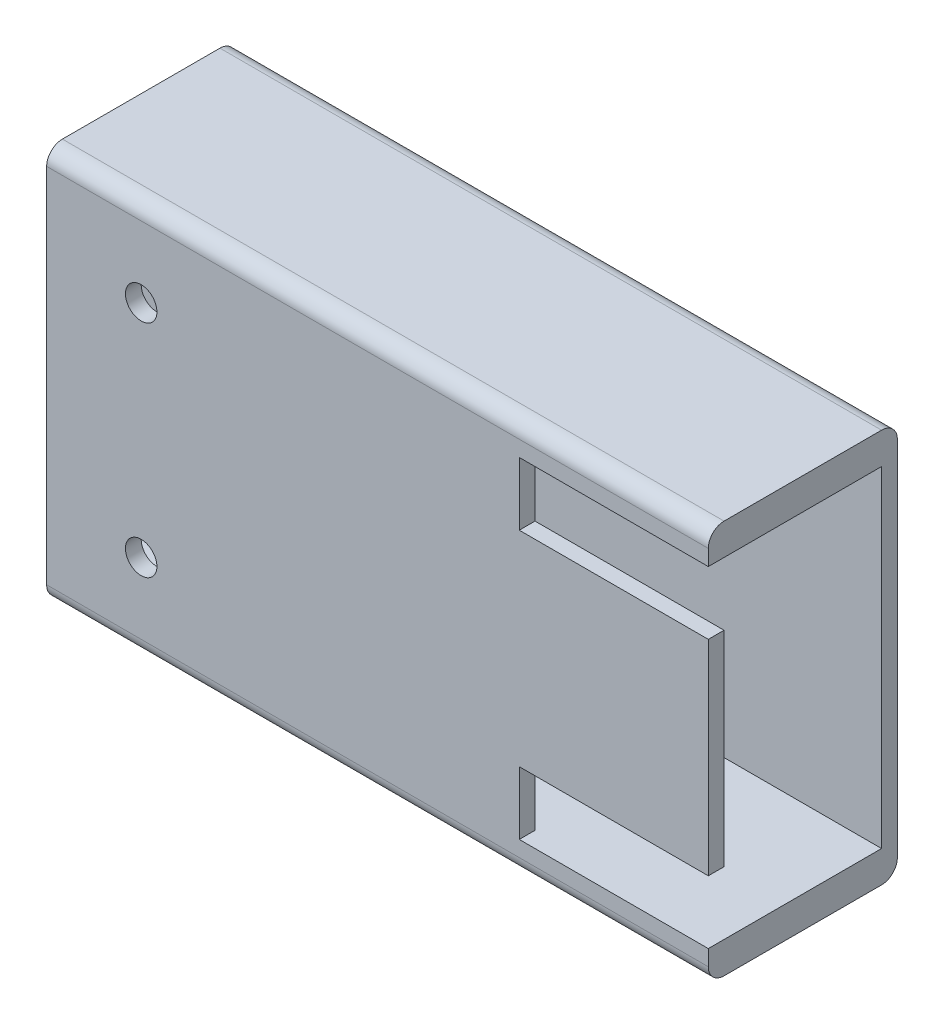
SolidWorks part; units mm, degrees
ref_plane "前视基准面" through (0, 0, 0) normal (0, 0, 1) x (1, 0, 0)
ref_plane "上视基准面" through (0, 0, 0) normal (0, 1, 0) x (1, 0, 0)
ref_plane "右视基准面" through (0, 0, 0) normal (1, 0, 0) x (0, 0, -1)
other "Configuration Table"
sketch "草图1" plane through (0, 0, 0) normal (0, 0, 1) x (1, 0, 0)
  line L0 (21, 12.5) -> (21, -12.5)
  line L1 (-19, 10.5) -> (19, 10.5) construction
  line L2 (-19, 10.5) -> (-19, -10.5) construction
  line L3 (-19, -10.5) -> (19, -10.5) construction
  line L4 (19, 10.5) -> (19, -10.5) construction
  line L5 (-21, -12.5) -> (21, -12.5)
  line L6 (-21, 12.5) -> (-21, -12.5)
  line L7 (-21, 12.5) -> (21, 12.5)
  dimension "D1" = 21
  dimension "D2" = 38
  dimension "D3" = 19
  dimension "D4" = 10.5
  dimension "D5" = 2
extrude "凸台-拉伸1" add sketch "草图1" along normal blind 12
sketch "草图3" plane through (21, 0, 0) normal (1, 0, 0) x (0, 0, -1)
  line L0 (0, -12.5) -> (0, 12.5) construction
  line L1 (-11, 10.5) -> (-1, 10.5)
  line L2 (-11, 10.5) -> (-11, -10.5)
  line L3 (-11, -10.5) -> (-1, -10.5)
  line L4 (-1, 10.5) -> (-1, -10.5)
  line L5 (-12, 12.5) -> (0, 12.5) construction
  dimension "D1" = 21
  dimension "D2" = 1
  dimension "D3" = 10
  dimension "D4" = 2
extrude "切除-拉伸1" cut sketch "草图3" against normal blind 41
sketch "草图4" plane through (-20, 0, 0) normal (1, 0, 0) x (0, 0, -1)
  line L0 (-11, 10.5) -> (-11, -10.5) construction
  line L1 (-11, 5) -> (-6, 5)
  line L2 (-11, 5) -> (-11, -5)
  line L3 (-11, -5) -> (-6, -5)
  line L4 (-6, 5) -> (-6, -5)
  dimension "D1" = 10
  dimension "D2" = 5
  dimension "D3" = 5
extrude "切除-拉伸2" cut sketch "草图4" against normal blind 10
sketch "草图5" plane through (0, 0, 12) normal (0, 0, 1) x (1, 0, 0)
  line L0 (21, 12.5) -> (-21, 12.5) construction
  line L1 (-20, 10.5) -> (-12, 10.5) construction
  line L2 (-20, 10.5) -> (-20, 6.5) construction
  line L3 (-20, 6.5) -> (-12, 6.5) construction
  line L4 (-12, 10.5) -> (-12, 6.5) construction
  line L5 (-21, 12.5) -> (-21, -12.5) construction
  line L6 (0, 0) -> (50000, 0) construction
  line L7 (-12, -10.5) -> (-12, -6.5) construction
  line L8 (-20, -6.5) -> (-12, -6.5) construction
  line L9 (-20, -10.5) -> (-20, -6.5) construction
  line L10 (-20, -10.5) -> (-12, -10.5) construction
  line L11 (0, 0) -> (0, 50000) construction
  line L16 (9, 10.5) -> (9, 6.5)
  line L17 (21, 6.5) -> (9, 6.5)
  line L18 (21, 10.5) -> (21, 6.5)
  line L19 (21, 10.5) -> (9, 10.5)
  line L20 (21, -12.5) -> (21, 12.5) construction
  line L21 (21, -10.5) -> (9, -10.5)
  line L22 (21, -10.5) -> (21, -6.5)
  line L23 (21, -6.5) -> (9, -6.5)
  line L24 (9, -10.5) -> (9, -6.5)
  point P27 (9, 6.5)
  dimension "D1" = 4
  dimension "D2" = 2
  dimension "D3" = 1
  dimension "D4" = 8
  dimension "D5" = 4
  dimension "D6" = 12
  dimension "D9" = 2
extrude "切除-拉伸3" cut sketch "草图5" against normal blind 10
sketch "草图6" plane through (0, 0, 12) normal (0, 0, 1) x (1, 0, 0)
  line L0 (-21, 12.5) -> (-21, -12.5) construction
  circle A0 centre (-15, 7) radius 1
  circle A1 centre (-15, -7) radius 1
  point P6 (0, 0)
  point P8 (0, 0)
  dimension "D1" = 6
  dimension "D2" = 2
  dimension "D4" = 7
  dimension "D5" = 2
  dimension "D3" = 14
extrude "切除-拉伸4" cut sketch "草图6" against normal blind 10 and the other way blind 10
fillet "圆角1" radius 1 4 edges at (0, -12.5, 0) (0, -12.5, 12) (0, 12.5, 0) (0, 12.5, 12)
